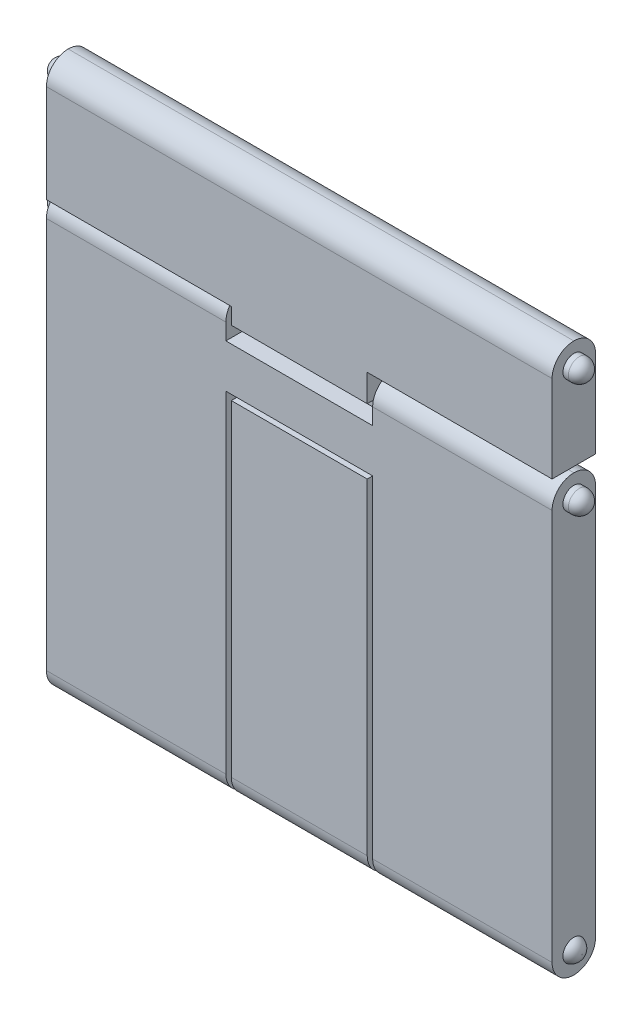
SolidWorks part; units mm, degrees
ref_plane "Front Plane" through (0, 0, 0) normal (0, 0, 1) x (1, 0, 0)
ref_plane "Top Plane" through (0, 0, 0) normal (0, 1, 0) x (1, 0, 0)
ref_plane "Right Plane" through (0, 0, 0) normal (1, 0, 0) x (0, 0, -1)
sketch "Sketch1" plane through (0, 0, 0) normal (0, 0, 1) x (1, 0, 0)
  line L1 (23.25, -25.25) -> (-23.25, -25.25)
  line L2 (23.25, -25.25) -> (23.25, 25.25)
  line L3 (23.25, 25.25) -> (-23.25, 25.25)
  line L4 (-23.25, -25.25) -> (-23.25, 25.25)
  line L5 (23.25, -25.25) -> (-23.25, 25.25) construction
  line L6 (23.25, 25.25) -> (-23.25, -25.25) construction
  point P0 (0, 0)
  dimension "D1" = 46.5
  dimension "D2" = 50.5
extrude "body" add sketch "Sketch1" along normal blind 4
sketch "Sketch2" plane through (0, 0, 4) normal (0, 0, 1) x (1, 0, 0)
  line L15 (-23.25, 15.25) -> (-6.25, 15.25)
  line L16 (-23.25, 25.25) -> (-23.25, -25.25) construction
  line L18 (-6.25, 15.25) -> (-6.25, -25.25)
  line L34 (-23.25, -25.25) -> (23.25, -25.25) construction
  line L35 (-6.25, -25.25) -> (-6.75, -25.25)
  line L36 (-6.75, -25.25) -> (-6.75, 14.75)
  line L37 (-6.75, 14.75) -> (-23.25, 14.75)
  line L38 (-23.25, 14.75) -> (-23.25, 15.25)
  line L39 (6.25, 15.25) -> (23.25, 15.25)
  line L40 (23.25, -25.25) -> (23.25, 25.25) construction
  line L41 (23.25, 15.25) -> (23.25, 14.75)
  line L42 (23.25, 14.75) -> (6.75, 14.75)
  line L43 (6.75, 14.75) -> (6.75, -25.25)
  line L44 (6.75, -25.25) -> (6.25, -25.25)
  line L45 (6.25, -25.25) -> (6.25, 15.25)
  line L46 (23.25, 25.25) -> (-23.25, 25.25) construction
  dimension "D1" = 10
  dimension "D2" = 0.5
  dimension "D3" = 0.5
  dimension "D4" = 0.5
  dimension "D5" = 0.5
  dimension "D6" = 16.5
  dimension "D7" = 16.5
  dimension "D8" = 90
extrude "body_cut" cut sketch "Sketch2" against normal blind 4
fillet "Fillet1" radius 2 4 edges at (-15, -25.25, 0) (-15, -25.25, 4) (-15, 14.75, 4) (-15, 14.75, 0)
fillet "Fillet2" radius 2 4 edges at (15, 14.75, 0) (15, -25.25, 0) (15, -25.25, 4) (15, 14.75, 4)
fillet "Fillet3" radius 2 4 edges at (0, 25.25, 0) (0, 25.25, 4) (0, -25.25, 0) (0, -25.25, 4)
sketch "Sketch4" plane through (23.25, 0, 0) normal (1, 0, 0) x (0, 0, -1)
  line L0 (-2, -25.25) -> (-2, 14.75) construction
  circle A0 centre (-2, -23.25) radius 1.25
  dimension "D2" = 2.5
  dimension "D1" = 2
extrude "hinge_hole_l" cut sketch "Sketch4" against normal blind 10 from offset 6.5 offset against normal yes
sketch "Sketch8" plane through (-23.25, 0, 0) normal (-1, 0, 0) x (0, 0, 1)
  line L0 (2, 14.75) -> (2, -25.25) construction
  arc A0 (4, 12.75) -> (2, 14.75) centre (2, 12.75) ccw construction
  circle A1 centre (2, -23.25) radius 1.25
  dimension "D2" = 2.5
  dimension "D1" = 2
extrude "hinge_hole_r" cut sketch "Sketch8" against normal blind 10 from offset 6.5 offset against normal yes
sketch "Sketch7" plane through (-6.25, 0, 0) normal (-1, 0, 0) x (0, 0, 1)
  line L0 (2, 14.75) -> (2, -25.25) construction
  circle A0 centre (2, -23.25) radius 0.9
  arc A1 (2, -25.25) -> (4, -23.25) centre (2, -23.25) ccw construction
  dimension "D2" = 1.8
  dimension "D1" = 2
extrude "hinge_rod" add sketch "Sketch7" against normal blind 26.5 from offset 7
sketch "Sketch9" plane through (0, 0, 4) normal (0, 0, 1) x (1, 0, 0)
  line L6 (-23.25, 12.75) -> (23.25, 12.75) construction
  line L7 (-23.25, 12.75) -> (-23.25, -23.25) construction
  line L8 (-6.75, 12.75) -> (-23.25, 12.75) construction
  line L9 (23.25, 12.75) -> (6.75, 12.75) construction
  line L10 (-6.25, 15.25) -> (-6.25, -25.25) construction
  line L11 (-6.25, 12.75) -> (6.25, 12.75)
  line L12 (-6.25, 12.75) -> (-6.25, 6.75)
  line L13 (-6.25, 6.75) -> (6.25, 6.75)
  line L14 (6.25, 12.75) -> (6.25, 6.75)
  line L15 (6.25, -25.25) -> (6.25, 15.25) construction
  dimension "D1" = 6
extrude "conn_cut" cut sketch "Sketch9" against normal blind 2
sketch "Sketch10" plane through (-6.75, 0, 0) normal (1, 0, 0) x (0, 0, -1)
  line L0 (-4, -25.25) -> (-4, 14.75) construction
  line L1 (-4, 7.25) -> (-2.5, 7.25)
  line L2 (-4, 7.25) -> (-4, 11.25)
  line L3 (-4, 11.25) -> (-2.5, 11.25)
  line L4 (-2.5, 7.25) -> (-2.5, 11.25)
  line L5 (-2, 14.75) -> (-4, 14.75) construction
  line L6 (-4, 14.75) -> (-4, 15.25) construction
  dimension "D1" = 4
  dimension "D2" = 3.5
  dimension "D3" = 1.5
extrude "conn_piece" add sketch "Sketch10" along normal blind 13.5
sketch "Sketch12" plane through (23.25, 0, 0) normal (1, 0, 0) x (0, 0, -1)
  line L0 (-2, 25.25) -> (-2, -25.25) construction
  line L1 (-2, 14.75) -> (0, 14.75) construction
  line L2 (0, 15.25) -> (0, -23.25) construction
  circle A0 centre (-2, 23.25) radius 1
  circle A1 centre (-2, 12.75) radius 1
  dimension "D1" = 2
  dimension "D2" = 2
  dimension "D3" = 2
  dimension "D4" = 2
extrude "bumps_l" add sketch "Sketch12" along normal blind 1.5
sketch "Sketch13" plane through (-23.25, 0, 0) normal (-1, 0, 0) x (0, 0, 1)
  line L0 (2, 25.25) -> (2, -25.25) construction
  line L1 (2, 14.75) -> (4, 14.75) construction
  line L2 (4, 14.75) -> (4, -25.25) construction
  line L3 (4, 15.25) -> (4, 14.75) construction
  arc A0 (0, -23.25) -> (2, -25.25) centre (2, -23.25) ccw construction
  circle A1 centre (2, 23.25) radius 1
  circle A2 centre (2, 12.75) radius 1
  dimension "D3" = 2
  dimension "D4" = 2
  dimension "D1" = 2
  dimension "D2" = 2
extrude "bumps_r" add sketch "Sketch13" along normal blind 1.5
sketch "Sketch14" plane through (23.25, 0, 0) normal (1, 0, 0) x (0, 0, -1)
  line L0 (-2, -25.25) -> (-2, 14.75) construction
  arc A0 (-4, -23.25) -> (-2, -25.25) centre (-2, -23.25) ccw construction
  circle A1 centre (-2, -23.25) radius 1
  dimension "D1" = 2
  dimension "D2" = 2
extrude "mini_bump_l" add sketch "Sketch14" along normal blind 0.75
sketch "Sketch15" plane through (-23.25, 0, 0) normal (-1, 0, 0) x (0, 0, 1)
  line L0 (2, 14.75) -> (2, -25.25) construction
  arc A0 (2, -25.25) -> (4, -23.25) centre (2, -23.25) ccw construction
  circle A1 centre (2, -23.25) radius 1
  dimension "D2" = 2
  dimension "D1" = 2
extrude "mini_bump_r" add sketch "Sketch15" along normal blind 0.75
fillet "Fillet6" radius 1 2 edges at (24.75, 23.25, 1) (-24.75, 23.25, 3)
fillet "Fillet7" radius 1 2 edges at (-24.75, 12.75, 3) (-24, -23.25, 3)
fillet "Fillet8" radius 1 2 edges at (24.75, 12.75, 1) (24, -23.25, 1)
sketch "Sketch16" plane through (-23.25, 0, 0) normal (-1, 0, 0) x (0, 0, 1)
  line L0 (2, 15.25) -> (2, -25.25) construction
  line L1 (0, 15.25) -> (4, 15.25) construction
  line L2 (0, -23.25) -> (0, 15.25) construction
  line L3 (4, -25.25) -> (4, 15.25) construction
  line L4 (0, 14.25) -> (0, 15.75)
  line L5 (0, 15.75) -> (4, 15.75)
  line L6 (4, 23.25) -> (4, 15.25) construction
  line L7 (4, 15.75) -> (4, 14.25)
  arc A0 (0, 14.25) -> (4, 14.25) centre (2, 12.75) cw
  dimension "D1" = 2.5
  dimension "D2" = 0.5
extrude "hook_material_r" add sketch "Sketch16" against normal blind 17
sketch "Sketch17" plane through (23.25, 0, 0) normal (1, 0, 0) x (0, 0, -1)
  line L0 (-2, 15.25) -> (-2, -25.25) construction
  line L1 (0, 15.25) -> (-4, 15.25) construction
  line L2 (-4, -25.25) -> (-4, 14.75) construction
  line L3 (0, 15.25) -> (0, -23.25) construction
  line L4 (0, 14.25) -> (0, 15.75)
  line L5 (0, 15.25) -> (0, 23.25) construction
  line L6 (0, 15.75) -> (-4, 15.75)
  line L7 (-4, 15.25) -> (-4, 23.25) construction
  line L9 (-4, 14.25) -> (-4, 15.75)
  line L11 (-4, 15.75) -> (-4, 14.25)
  arc A0 (-4, 14.25) -> (0, 14.25) centre (-2, 12.75) cw
  dimension "D1" = 0.5
  dimension "D2" = 2.5
